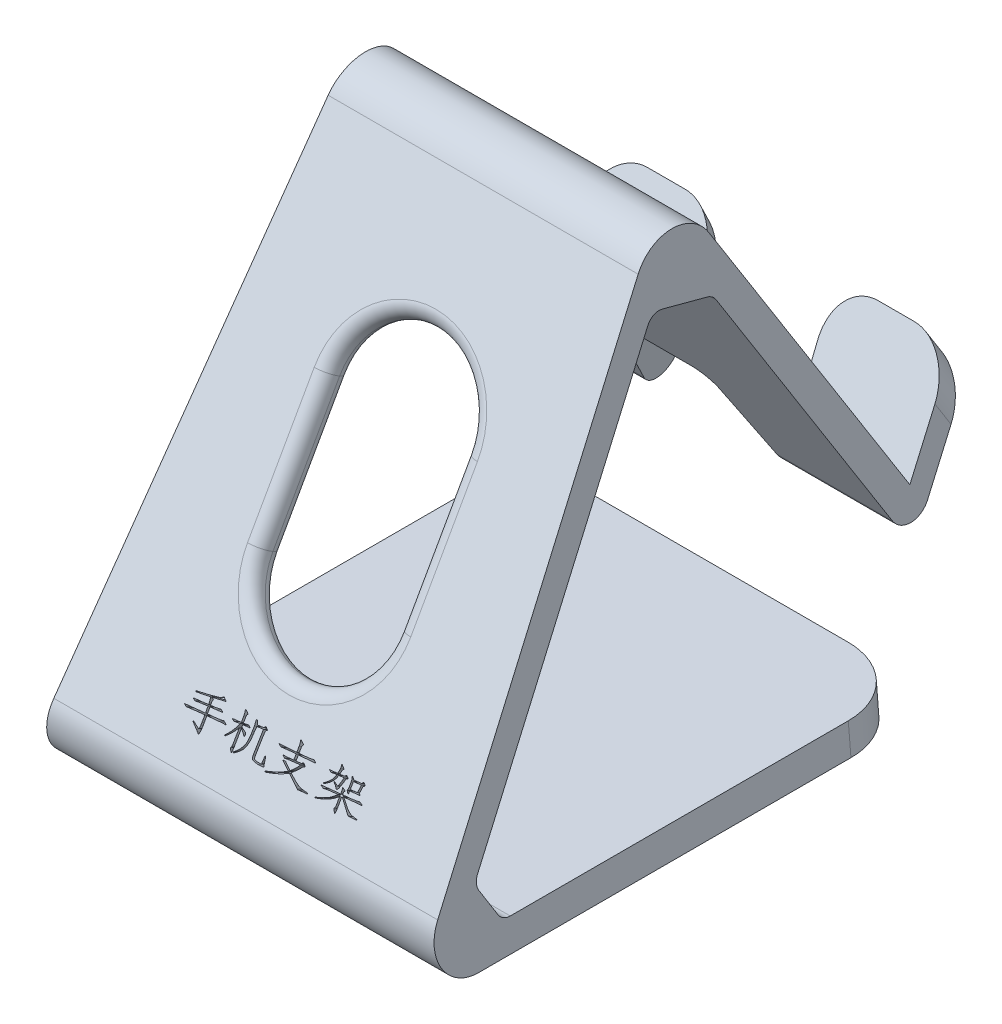
SolidWorks part; units mm, degrees
material "PPS"
ref_plane "前视基准面" through (0, 0, 0) normal (0, 0, 1) x (1, 0, 0)
ref_plane "上视基准面" through (0, 0, 0) normal (0, 1, 0) x (1, 0, 0)
ref_plane "右视基准面" through (0, 0, 0) normal (1, 0, 0) x (0, 0, -1)
other "Configuration Table"
sketch "草图1" plane through (0, 0, 0) normal (1, 0, 0) x (0, 0, -1)
  line L0 (0, 0) -> (0, -4.5)
  line L1 (0, -4.5) -> (-75, -4.5)
  line L2 (-75, -4.5) -> (-30, 75.5)
  line L3 (-30, 75.5) -> (1.1057, 23.4782)
  line L4 (1.1057, 23.4782) -> (8.7047, 36.9876)
  line L5 (8.7047, 36.9876) -> (10.7739, 33.5271)
  line L6 (10.7739, 33.5271) -> (0.9157, 16.0015)
  line L7 (0.9157, 16.0015) -> (-29.8943, 67.5289)
  line L8 (-29.8943, 67.5289) -> (-67.8794, 0)
  line L9 (-67.8794, 0) -> (0, 0)
  dimension "D1" = 4.5
  dimension "D2" = 75
  dimension "D3" = 80
  dimension "D4" = 4
  dimension "D5" = 15.5
  dimension "D6" = 3.5
  dimension "D7" = 4
  dimension "D8" = 45
  dimension "D9" = 31
  dimension "D10" = 28
extrude "凸台-拉伸1" add sketch "草图1" against normal blind 58
sketch "草图3" plane through (0, 0, 0) normal (0, 0, -1) x (-1, 0, 0)
  line L0 (7, 75.5) -> (0, -4.5)
  line L1 (58, 75.5) -> (0, 75.5) construction
  line L2 (0, -4.5) -> (0, 75.5)
  line L3 (0, 75.5) -> (7, 75.5)
  line L4 (29, 75.5) -> (29, -4.5) construction
  line L5 (58, -4.5) -> (0, -4.5) construction
  line L6 (58, -4.5) -> (58, 75.5)
  line L7 (51, 75.5) -> (58, -4.5)
  line L8 (58, 75.5) -> (51, 75.5)
  dimension "D1" = 7
extrude "切除-拉伸2" cut sketch "草图3" against normal through all both and the other way through all
sketch "草图4" plane through (0, 13.5753, -22.7037) normal (0, 0.5132, -0.8583) x (-1, 0, 0)
  line L0 (40.9207, 6.8334) -> (16.9207, 6.8334)
  line L1 (16.9207, 6.8334) -> (21.9207, 32.8334)
  line L2 (21.9207, 32.8334) -> (35.9207, 32.8334)
  line L4 (28.9207, 32.8334) -> (28.9207, 97.1317) construction
  line L5 (40.9207, 6.8334) -> (35.9207, 32.8334)
  dimension "D1" = 7
extrude "切除-拉伸3" cut sketch "草图4" against normal up to next and the other way through all
fillet "圆角2" radius 10 2 edges at (-57.8031, -2.25, 0) (-0.1969, -2.25, 0)
chamfer "倒角2" distance 7 angle 60 1 edges at (-29, 0, 67.8794) first distance on face at (-29, 33.7645, 48.8868)
chamfer "倒角3" distance 10 angle 45 1 edges at (-29, 67.5289, 29.8943) first distance on face at (-28.9604, 33.0824, 9.2975)
fillet "圆角3" radius 6 2 edges at (-29, -4.5, 75) (-29, 75.5, 30)
fillet "圆角4" radius 6 4 edges at (-37.3767, 35.2573, -9.7393) (-54.5212, 35.2573, -9.7393) (-20.4648, 35.2573, -9.7393) (-3.4788, 35.2573, -9.7393)
fillet "圆角6" radius 3 2 edges at (-47.9451, 16.0015, -0.9157) (-9.9756, 16.0015, -0.9157)
sketch "草图5" plane through (0, -4.5, 0) normal (0, -1, 0) x (1, 0, 0)
  line L0 (-29, 0) -> (-29, 72.6515) construction
  line L1 (-47.9618, 0) -> (-10.0382, 0) construction
  circle A0 centre (-47.9618, 10) radius 5
  circle A1 centre (-10.0382, 10) radius 5
  circle A2 centre (-29, 55) radius 5
  dimension "D1" = 10
  dimension "D2" = 55
extrude "凸台-拉伸2" add sketch "草图5" along normal blind 2
sketch "草图6" plane through (0, 30.9659, 55.0504) normal (0, 0.4903, 0.8716) x (1, 0, 0)
  line L1 (-19, 14.5674) -> (-19, -5.4326)
  line L2 (-39, 14.5674) -> (-39, -5.4326)
  line L3 (-57.2176, -30.4326) -> (-0.7824, -30.4326) construction
  arc A0 (-19, 14.5674) -> (-39, 14.5674) centre (-29, 14.5674) ccw
  arc A1 (-39, -5.4326) -> (-19, -5.4326) centre (-29, -5.4326) ccw
  point P2 (-29, 4.5674)
  dimension "D2" = 10
  dimension "D1" = 20
  dimension "D3" = 35
extrude "切除-拉伸4" cut sketch "草图6" against normal up to next
sketch "草图8" plane through (0, 30.9659, 55.0504) normal (0, 0.4903, 0.8716) x (1, 0, 0)
  text T0 "手   机   支    架" font "汉仪长仿宋体" height 3.5
extrude "切除-拉伸5" cut sketch "草图8" against normal blind 1
fillet "圆角7" radius 3 2 edges at (-35.9207, 33.824, 7.4107) (-21.9207, 33.824, 7.4107)
sketch "草图9" plane through (0, 6.6703, -11.1556) normal (0, 0.5132, -0.8583) x (-1, 0, 0)
  line L0 (18.1205, 47.847) -> (23.5111, 45.4499)
  line L1 (25.5334, 46.0295) -> (28.3422, 49.7877)
  line L2 (25.5334, 46.0295) -> (25.4004, 45.8966)
  line L3 (32.6957, 45.7168) -> (28.5502, 42.7172)
  line L4 (18.651, 43.4734) -> (22.1806, 41.9704)
  line L5 (22.1806, 41.9704) -> (22.3025, 41.8839)
  line L6 (23.5111, 45.4499) -> (23.7454, 45.4499)
  circle A0 centre (29.1661, 46.968) radius 11.0805
  circle A1 centre (25.3708, 42.7172) radius 3.1795
  circle A2 centre (32.6957, 50.0801) radius 4.3633
  circle A3 centre (32.6957, 50.0801) radius 2.2065
  circle A4 centre (32.6957, 50.0801) radius 2.8904
  circle A5 centre (25.3708, 42.7172) radius 1.917
  circle A6 centre (25.3708, 42.7172) radius 2.4337
sketch "草图14" plane through (0, 6.6703, -11.1556) normal (0, 0.5132, -0.8583) x (-1, 0, 0)
extrude "切除-拉伸10" cut sketch "草图9" against normal blind 1 contours A2 L3 A1 L5 L4 A0 L0 L6 L2 L1 | A6 A5 | A4 A3 region at (-29.5935, 56.2158, 18.4693) region at (-29.887, 49.6528, 14.5451) region at (-23.0059, 43.3334, 10.7665)
fillet "圆角8" radius 2 4 edges at (-29, 58.9462, 24.7624) (-29, 61.1415, 33.4873) (-29, 0, 60.8333) (-29, 6.101, 64.4475)
fillet "圆角9" radius 2 4 edges at (-29, 50.4172, 39.5197) (-19, 32.9857, 49.3249) (-29, 15.5542, 59.1301) (-39, 32.9857, 49.3249)
fillet "圆角10" radius 2 4 edges at (-29, 17.5152, 62.6164) (-39, 34.9467, 52.8112) (-29, 52.3782, 43.006) (-19, 34.9467, 52.8112)
